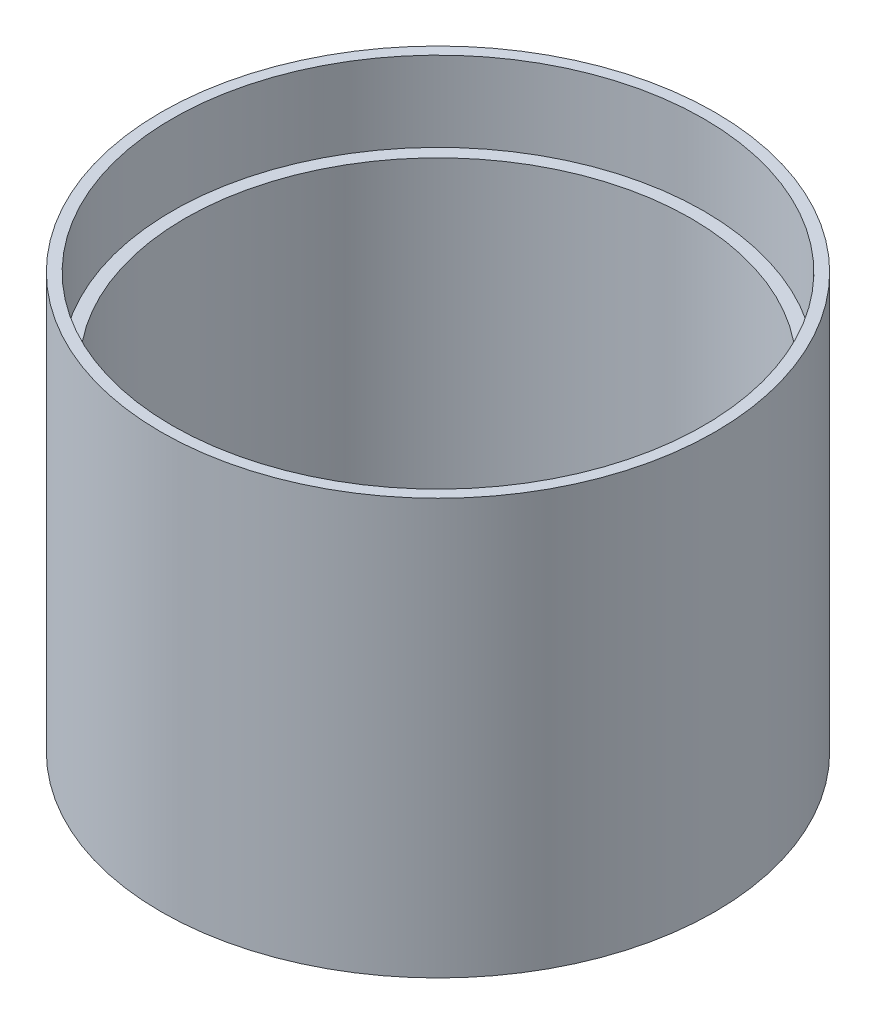
SolidWorks part; units mm, degrees
ref_plane "Front Plane" through (0, 0, 0) normal (0, 0, 1) x (1, 0, 0)
ref_plane "Top Plane" through (0, 0, 0) normal (0, 1, 0) x (1, 0, 0)
ref_plane "Right Plane" through (0, 0, 0) normal (1, 0, 0) x (0, 0, -1)
sketch "Sketch1" plane through (0, 0, 0) normal (0, 1, 0) x (1, 0, 0)
  circle A0 centre (0, 0) radius 26
  circle A1 centre (0, 0) radius 24.95
  dimension "D1" = 52
  dimension "D2" = 49.9
extrude "Boss-Extrude1" add sketch "Sketch1" along normal blind 7.5
sketch "Sketch2" plane through (0, 0, 0) normal (0, -1, 0) x (1, 0, 0)
  circle A0 centre (0, 0) radius 26
  circle A1 centre (0, 0) radius 23.75
  circle A2 centre (0, 0) radius 26 construction
  dimension "D1" = 47.5
extrude "Boss-Extrude2" add sketch "Sketch2" along normal blind 31.5
sketch "Sketch3" plane through (0, -31.5, 0) normal (0, -1, 0) x (1, 0, 0)
  circle A0 centre (0, 0) radius 23.75
  circle A1 centre (0, 0) radius 23.75 construction
extrude "Boss-Extrude3" add sketch "Sketch3" against normal blind 1
sketch "Sketch4" plane through (0, -31.5, 0) normal (0, -1, 0) x (1, 0, 0)
  circle A0 centre (0, 0) radius 3
  dimension "D1" = 6
extrude "Cut-Extrude1" cut sketch "Sketch4" against normal blind 1
